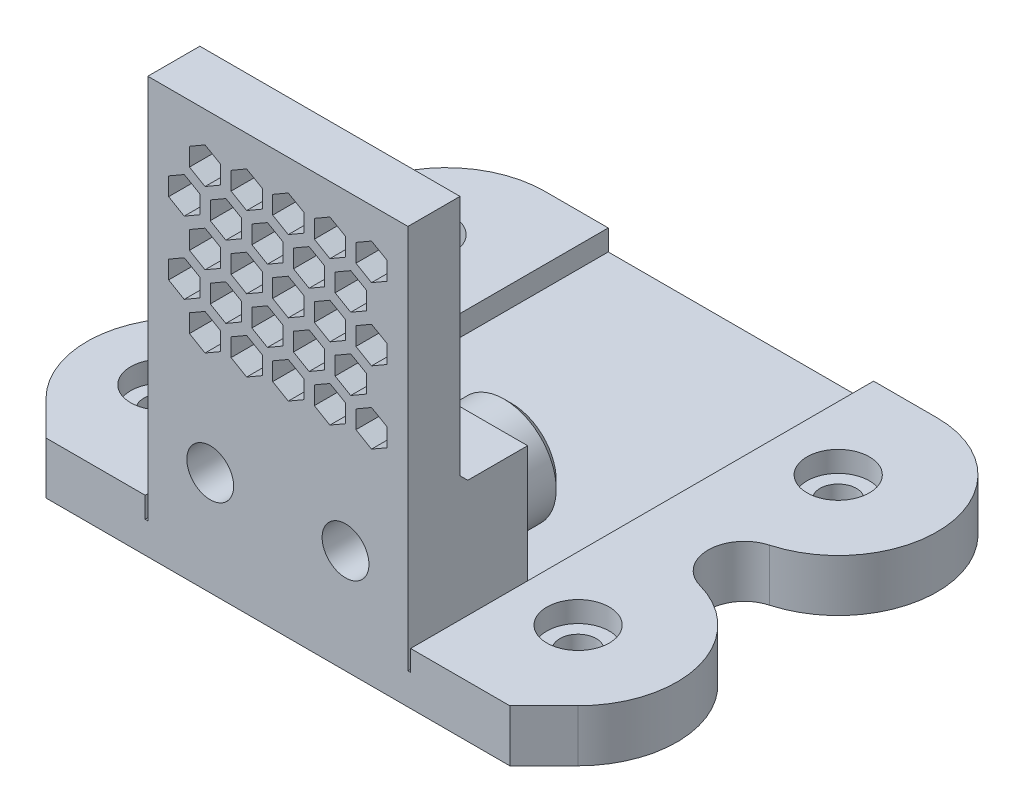
SolidWorks part; units mm, degrees
ref_plane "Front Plane" through (0, 0, 0) normal (0, 0, 1) x (1, 0, 0)
ref_plane "Top Plane" through (0, 0, 0) normal (0, 1, 0) x (1, 0, 0)
ref_plane "Right Plane" through (0, 0, 0) normal (1, 0, 0) x (0, 0, -1)
sketch "Sketch1" plane through (0, 0, 0) normal (1, 0, 0) x (0, 0, -1)
  line L0 (0, 0) -> (0, 40)
  line L1 (0, 40) -> (5, 40)
  line L2 (5, 40) -> (5, 16.75)
  line L3 (5, 16.75) -> (5.75, 16)
  line L4 (5.75, 16) -> (11.5, 16)
  line L5 (11.5, 16) -> (11.5, 3)
  line L6 (11.5, 3) -> (44.5, 3)
  line L7 (44.5, 3) -> (44.5, 0)
  line L8 (44.5, 0) -> (0, 0)
  line L9 (11.5, 3) -> (44, 3) construction
  line L10 (11.5, 16) -> (11.5, 3) construction
  line L11 (7, 16) -> (11.5, 16) construction
  dimension "D1" = 40
  dimension "D2" = 6.5
  dimension "D3" = 135
  dimension "D4" = 0.75
  dimension "D5" = 33
extrude "Boss-Extrude1" add sketch "Sketch1" against normal blind 25
sketch "Sketch2" plane through (0, 0, -11.5) normal (0, 0, -1) x (-1, 0, 0)
  circle A0 centre (6, 10) radius 2 construction
  circle A1 centre (6, 10) radius 5.25 construction
  circle A2 centre (6, 10) radius 5
  circle A3 centre (6, 10) radius 2.25
  circle A4 centre (19, 10) radius 5.4 construction
  circle A5 centre (6, 10) radius 2.75 construction
  circle A6 centre (19, 10) radius 2.25
  circle A7 centre (19, 10) radius 5
  dimension "D3" = 4
  dimension "D4" = 10
  dimension "D1" = 0.25
  dimension "D2" = 0.25
extrude "Boss-Extrude2" add sketch "Sketch2" along normal blind 4.5
chamfer "Chamfer1" distance 0.75 angle 45 2 edges at (-6, 15, -16) (-19, 15, -16)
extrude "Cut-Extrude1" cut sketch "Sketch2<2>" against normal up to next contours A3 | A6 region at (-6, 10, -11.5) region at (-19, 10, -11.5)
sketch "Sketch2<2>" plane through (0, 0, -11.5) normal (0, 0, -1) x (-1, 0, 0) same geometry as "Sketch2"
sketch "Sketch3" plane through (0, 3, 0) normal (0, 1, 0) x (1, 0, 0)
  line L0 (0, 44.5) -> (6.35, 44.5)
  line L1 (-12.5, 44.5) -> (-12.5, 11.5) construction
  line L2 (-25, 44.5) -> (0, 44.5) construction
  line L3 (-25, 11.5) -> (0, 11.5) construction
  line L4 (6.35, 44.5) -> (6.35, 0.5) construction
  line L5 (13.0675, 3.2825) -> (9.785, 0)
  line L6 (9.785, 0) -> (0, 0)
  line L7 (0, 0) -> (0, 11.5)
  line L8 (0, 11.5) -> (-25, 11.5)
  line L9 (0, 44.5) -> (-25, 44.5)
  line L10 (-25, 0) -> (-25, 11.5)
  line L11 (-34.785, 0) -> (-25, 0)
  line L12 (-38.0675, 3.2825) -> (-34.785, 0)
  line L13 (-25, 44.5) -> (-31.35, 44.5)
  arc A0 (6.35, 44.5) -> (8.8936, 25.8469) centre (6.35, 35) cw
  arc A1 (8.8936, 25.8469) -> (8.8936, 19.1531) centre (9.8237, 22.5) ccw
  arc A2 (8.8936, 19.1531) -> (13.0675, 3.2825) centre (6.35, 10) cw
  circle A3 centre (-33.65, 10) radius 1.75 construction
  circle A4 centre (6.35, 10) radius 1.75
  arc A6 (13.0675, 3.2825) -> (6.35, 0.5) centre (6.35, 10) cw construction
  circle A7 centre (6.35, 35) radius 1.75
  arc A10 (-33.8936, 19.1531) -> (-38.0675, 3.2825) centre (-31.35, 10) ccw
  arc A11 (-33.8936, 25.8469) -> (-33.8936, 19.1531) centre (-34.8237, 22.5) cw
  arc A12 (-31.35, 44.5) -> (-33.8936, 25.8469) centre (-31.35, 35) ccw
  circle A13 centre (6.35, 35) radius 1.75 construction
  circle A14 centre (-33.65, 10) radius 1.75
  circle A15 centre (-33.65, 35) radius 1.75
  circle A18 centre (6.35, 10) radius 1.75 construction
  circle A19 centre (-33.65, 35) radius 1.75 construction
  point P22 (6.35, 22.5)
  point P37 (-31.35, 22.5)
  dimension "D2" = 3.5
  dimension "D1" = 135
extrude "Boss-Extrude3" add sketch "Sketch3" against normal up to surface (3 mm away) up to face at (-12.5, 0, -22.25)
sketch "Sketch4" plane through (0, 3, 0) normal (0, 1, 0) x (1, 0, 0)
  line L0 (-34.785, 0) -> (-25, 0) construction
  line L1 (-38.0675, 3.2825) -> (-34.785, 0) construction
  line L2 (-31.35, 44.5) -> (6.35, 44.5) construction
  line L3 (9.785, 0) -> (13.0675, 3.2825) construction
  line L5 (-34.785, 0) -> (-25.25, 0)
  line L6 (-38.0675, 3.2825) -> (-34.785, 0)
  line L7 (-31.35, 44.5) -> (-25.25, 44.5)
  line L8 (9.785, 0) -> (13.0675, 3.2825)
  line L10 (-25, 0) -> (-25, 11.5) construction
  line L11 (0, 11.5) -> (0, 0) construction
  line L20 (-25, 0) -> (-25, 11.5) construction
  line L21 (0, 11.5) -> (0, 0) construction
  line L22 (0.25, 44.5) -> (0.25, 0)
  line L23 (0.25, 11.5) -> (0.25, 0) construction
  line L24 (-25.25, 0) -> (-25.25, 44.5)
  line L25 (-25.25, 0) -> (-25.25, 11.5) construction
  line L26 (0.25, 44.5) -> (6.35, 44.5)
  line L27 (-25.25, 44.5) -> (0.25, 44.5) construction
  line L28 (0.25, 0) -> (9.785, 0)
  arc A0 (-33.8936, 19.1531) -> (-38.0675, 3.2825) centre (-31.35, 10) ccw construction
  arc A1 (-33.8936, 19.1531) -> (-33.8936, 25.8469) centre (-34.8237, 22.5) ccw construction
  arc A2 (-31.35, 44.5) -> (-33.8936, 25.8469) centre (-31.35, 35) ccw construction
  arc A3 (8.8936, 25.8469) -> (6.35, 44.5) centre (6.35, 35) ccw construction
  arc A4 (8.8936, 25.8469) -> (8.8936, 19.1531) centre (9.8237, 22.5) ccw construction
  arc A5 (13.0675, 3.2825) -> (8.8936, 19.1531) centre (6.35, 10) ccw construction
  arc A6 (-33.8936, 19.1531) -> (-38.0675, 3.2825) centre (-31.35, 10) ccw
  arc A7 (-33.8936, 19.1531) -> (-33.8936, 25.8469) centre (-34.8237, 22.5) ccw
  arc A8 (-31.35, 44.5) -> (-33.8936, 25.8469) centre (-31.35, 35) ccw
  arc A9 (8.8936, 25.8469) -> (6.35, 44.5) centre (6.35, 35) ccw
  arc A10 (8.8936, 25.8469) -> (8.8936, 19.1531) centre (9.8237, 22.5) ccw
  arc A11 (13.0675, 3.2825) -> (8.8936, 19.1531) centre (6.35, 10) ccw
  circle A12 centre (6.35, 10) radius 2.75 construction
  circle A13 centre (6.35, 35) radius 3
  circle A16 centre (6.35, 10) radius 3
  circle A19 centre (-33.65, 10) radius 3
  circle A20 centre (-33.65, 35) radius 3
  circle A21 centre (-33.65, 35) radius 1.75 construction
  circle A22 centre (-33.65, 10) radius 1.75 construction
  line M26 (0, 0) -> (9.785, 0)
  line M27 (9.785, 0) -> (13.0675, 3.2825)
  arc M28 (13.0675, 3.2825) -> (8.8936, 19.1531) centre (6.35, 10) ccw
  arc M29 (8.8936, 19.1531) -> (8.8936, 25.8469) centre (9.8237, 22.5) cw
  arc M30 (8.8936, 25.8469) -> (6.35, 44.5) centre (6.35, 35) ccw
  line M31 (6.35, 44.5) -> (-31.35, 44.5)
  arc M32 (-31.35, 44.5) -> (-33.8936, 25.8469) centre (-31.35, 35) ccw
  arc M33 (-33.8936, 25.8469) -> (-33.8936, 19.1531) centre (-34.8237, 22.5) cw
  arc M34 (-33.8936, 19.1531) -> (-38.0675, 3.2825) centre (-31.35, 10) ccw
  line M35 (-38.0675, 3.2825) -> (-34.785, 0)
  line M36 (-34.785, 0) -> (-25, 0)
  dimension "D1" = 0.25
  dimension "D2" = 0.25
  dimension "D4" = 5.5
  dimension "D3" = 0.25
extrude "Boss-Extrude4" add sketch "Sketch4" along normal blind 2 contours L22 A16 A13 M31 M26 M27 M28 M29 M30 | A20 L24 A19 M31 M32 M33 M34 M35 M36 region at (-36.0928, 3, -1.9747) region at (3.3, 3, -44.0284)
sketch "Sketch5" plane through (0, 0, -5) normal (0, 0, -1) x (-1, 0, 0)
  line L0 (2, 37.0353) -> (0, 37.0353) construction
  line L1 (3.5, 19.7147) -> (5, 20.5808)
  line L2 (5, 20.5808) -> (5, 22.3128)
  line L3 (5, 22.3128) -> (3.5, 23.1788)
  line L4 (3.5, 23.1788) -> (2, 22.3128)
  line L5 (2, 22.3128) -> (2, 20.5808)
  line L6 (2, 20.5808) -> (3.5, 19.7147)
  line L7 (2, 19.7147) -> (23, 19.7147) construction
  line L8 (2, 19.7147) -> (2, 37.0353) construction
  line L9 (2, 37.0353) -> (23, 37.0353) construction
  line L11 (0, 16.75) -> (0, 40) construction
  line L12 (2, 40) -> (2, 37.0353) construction
  line L13 (25, 40) -> (0, 40) construction
  line L14 (25, 19.7147) -> (23, 19.7147) construction
  line L15 (25, 16.75) -> (25, 40) construction
  line L16 (23, 19.7147) -> (23, 16.75) construction
  line L17 (25, 16.75) -> (0, 16.75) construction
  line L60 (3.5, 21.4468) -> (-5.5, 37.0353) construction
  line L61 (-5.5, 37.0353) -> (0, 37.0353) construction
  line L302 (9, 22.3128) -> (7.5, 23.1788)
  line L303 (9, 20.5808) -> (9, 22.3128)
  line L304 (7.5, 19.7147) -> (9, 20.5808)
  line L305 (6, 20.5808) -> (7.5, 19.7147)
  line L306 (6, 22.3128) -> (6, 20.5808)
  line L307 (7.5, 23.1788) -> (6, 22.3128)
  line L308 (13, 22.3128) -> (11.5, 23.1788)
  line L309 (13, 20.5808) -> (13, 22.3128)
  line L310 (11.5, 19.7147) -> (13, 20.5808)
  line L311 (10, 20.5808) -> (11.5, 19.7147)
  line L312 (10, 22.3128) -> (10, 20.5808)
  line L313 (11.5, 23.1788) -> (10, 22.3128)
  line L314 (17, 22.3128) -> (15.5, 23.1788)
  line L315 (17, 20.5808) -> (17, 22.3128)
  line L316 (15.5, 19.7147) -> (17, 20.5808)
  line L317 (14, 20.5808) -> (15.5, 19.7147)
  line L318 (14, 22.3128) -> (14, 20.5808)
  line L319 (15.5, 23.1788) -> (14, 22.3128)
  line L320 (21, 22.3128) -> (19.5, 23.1788)
  line L321 (21, 20.5808) -> (21, 22.3128)
  line L322 (19.5, 19.7147) -> (21, 20.5808)
  line L323 (18, 20.5808) -> (19.5, 19.7147)
  line L324 (18, 22.3128) -> (18, 20.5808)
  line L325 (19.5, 23.1788) -> (18, 22.3128)
  line L326 (25, 22.3128) -> (23.5, 23.1788) [skipped]
  line L327 (25, 20.5808) -> (25, 22.3128) [skipped]
  line L328 (23.5, 19.7147) -> (25, 20.5808) [skipped]
  line L329 (22, 20.5808) -> (23.5, 19.7147) [skipped]
  line L330 (22, 22.3128) -> (22, 20.5808) [skipped]
  line L331 (23.5, 23.1788) -> (22, 22.3128) [skipped]
  line L332 (29, 22.3128) -> (27.5, 23.1788) [skipped]
  line L333 (29, 20.5808) -> (29, 22.3128) [skipped]
  line L334 (27.5, 19.7147) -> (29, 20.5808) [skipped]
  line L335 (26, 20.5808) -> (27.5, 19.7147) [skipped]
  line L336 (26, 22.3128) -> (26, 20.5808) [skipped]
  line L337 (27.5, 23.1788) -> (26, 22.3128) [skipped]
  line L338 (7, 25.7769) -> (5.5, 26.6429)
  line L339 (7, 24.0449) -> (7, 25.7769)
  line L340 (5.5, 23.1788) -> (7, 24.0449)
  line L341 (4, 24.0449) -> (5.5, 23.1788)
  line L342 (4, 25.7769) -> (4, 24.0449)
  line L343 (5.5, 26.6429) -> (4, 25.7769)
  line L344 (11, 25.7769) -> (9.5, 26.6429)
  line L345 (11, 24.0449) -> (11, 25.7769)
  line L346 (9.5, 23.1788) -> (11, 24.0449)
  line L347 (8, 24.0449) -> (9.5, 23.1788)
  line L348 (8, 25.7769) -> (8, 24.0449)
  line L349 (9.5, 26.6429) -> (8, 25.7769)
  line L350 (15, 25.7769) -> (13.5, 26.6429)
  line L351 (15, 24.0449) -> (15, 25.7769)
  line L352 (13.5, 23.1788) -> (15, 24.0449)
  line L353 (12, 24.0449) -> (13.5, 23.1788)
  line L354 (12, 25.7769) -> (12, 24.0449)
  line L355 (13.5, 26.6429) -> (12, 25.7769)
  line L356 (19, 25.7769) -> (17.5, 26.6429)
  line L357 (19, 24.0449) -> (19, 25.7769)
  line L358 (17.5, 23.1788) -> (19, 24.0449)
  line L359 (16, 24.0449) -> (17.5, 23.1788)
  line L360 (16, 25.7769) -> (16, 24.0449)
  line L361 (17.5, 26.6429) -> (16, 25.7769)
  line L362 (23, 25.7769) -> (21.5, 26.6429)
  line L363 (23, 24.0449) -> (23, 25.7769)
  line L364 (21.5, 23.1788) -> (23, 24.0449)
  line L365 (20, 24.0449) -> (21.5, 23.1788)
  line L366 (20, 25.7769) -> (20, 24.0449)
  line L367 (21.5, 26.6429) -> (20, 25.7769)
  line L368 (27, 25.7769) -> (25.5, 26.6429) [skipped]
  line L369 (27, 24.0449) -> (27, 25.7769) [skipped]
  line L370 (25.5, 23.1788) -> (27, 24.0449) [skipped]
  line L371 (24, 24.0449) -> (25.5, 23.1788) [skipped]
  line L372 (24, 25.7769) -> (24, 24.0449) [skipped]
  line L373 (25.5, 26.6429) -> (24, 25.7769) [skipped]
  line L374 (5, 29.241) -> (3.5, 30.1071)
  line L375 (5, 27.509) -> (5, 29.241)
  line L376 (3.5, 26.6429) -> (5, 27.509)
  line L377 (2, 27.509) -> (3.5, 26.6429)
  line L378 (2, 29.241) -> (2, 27.509)
  line L379 (3.5, 30.1071) -> (2, 29.241)
  line L380 (9, 29.241) -> (7.5, 30.1071)
  line L381 (9, 27.509) -> (9, 29.241)
  line L382 (7.5, 26.6429) -> (9, 27.509)
  line L383 (6, 27.509) -> (7.5, 26.6429)
  line L384 (6, 29.241) -> (6, 27.509)
  line L385 (7.5, 30.1071) -> (6, 29.241)
  line L386 (13, 29.241) -> (11.5, 30.1071)
  line L387 (13, 27.509) -> (13, 29.241)
  line L388 (11.5, 26.6429) -> (13, 27.509)
  line L389 (10, 27.509) -> (11.5, 26.6429)
  line L390 (10, 29.241) -> (10, 27.509)
  line L391 (11.5, 30.1071) -> (10, 29.241)
  line L392 (17, 29.241) -> (15.5, 30.1071)
  line L393 (17, 27.509) -> (17, 29.241)
  line L394 (15.5, 26.6429) -> (17, 27.509)
  line L395 (14, 27.509) -> (15.5, 26.6429)
  line L396 (14, 29.241) -> (14, 27.509)
  line L397 (15.5, 30.1071) -> (14, 29.241)
  line L398 (21, 29.241) -> (19.5, 30.1071)
  line L399 (21, 27.509) -> (21, 29.241)
  line L400 (19.5, 26.6429) -> (21, 27.509)
  line L401 (18, 27.509) -> (19.5, 26.6429)
  line L402 (18, 29.241) -> (18, 27.509)
  line L403 (19.5, 30.1071) -> (18, 29.241)
  line L404 (25, 29.241) -> (23.5, 30.1071) [skipped]
  line L405 (25, 27.509) -> (25, 29.241) [skipped]
  line L406 (23.5, 26.6429) -> (25, 27.509) [skipped]
  line L407 (22, 27.509) -> (23.5, 26.6429) [skipped]
  line L408 (22, 29.241) -> (22, 27.509) [skipped]
  line L409 (23.5, 30.1071) -> (22, 29.241) [skipped]
  line L410 (3, 32.7051) -> (1.5, 33.5712) [skipped]
  line L411 (3, 30.9731) -> (3, 32.7051) [skipped]
  line L412 (1.5, 30.1071) -> (3, 30.9731) [skipped]
  line L413 (0, 30.9731) -> (1.5, 30.1071) [skipped]
  line L414 (0, 32.7051) -> (0, 30.9731) [skipped]
  line L415 (1.5, 33.5712) -> (0, 32.7051) [skipped]
  line L416 (7, 32.7051) -> (5.5, 33.5712)
  line L417 (7, 30.9731) -> (7, 32.7051)
  line L418 (5.5, 30.1071) -> (7, 30.9731)
  line L419 (4, 30.9731) -> (5.5, 30.1071)
  line L420 (4, 32.7051) -> (4, 30.9731)
  line L421 (5.5, 33.5712) -> (4, 32.7051)
  line L422 (11, 32.7051) -> (9.5, 33.5712)
  line L423 (11, 30.9731) -> (11, 32.7051)
  line L424 (9.5, 30.1071) -> (11, 30.9731)
  line L425 (8, 30.9731) -> (9.5, 30.1071)
  line L426 (8, 32.7051) -> (8, 30.9731)
  line L427 (9.5, 33.5712) -> (8, 32.7051)
  line L428 (15, 32.7051) -> (13.5, 33.5712)
  line L429 (15, 30.9731) -> (15, 32.7051)
  line L430 (13.5, 30.1071) -> (15, 30.9731)
  line L431 (12, 30.9731) -> (13.5, 30.1071)
  line L432 (12, 32.7051) -> (12, 30.9731)
  line L433 (13.5, 33.5712) -> (12, 32.7051)
  line L434 (19, 32.7051) -> (17.5, 33.5712)
  line L435 (19, 30.9731) -> (19, 32.7051)
  line L436 (17.5, 30.1071) -> (19, 30.9731)
  line L437 (16, 30.9731) -> (17.5, 30.1071)
  line L438 (16, 32.7051) -> (16, 30.9731)
  line L439 (17.5, 33.5712) -> (16, 32.7051)
  line L440 (23, 32.7051) -> (21.5, 33.5712)
  line L441 (23, 30.9731) -> (23, 32.7051)
  line L442 (21.5, 30.1071) -> (23, 30.9731)
  line L443 (20, 30.9731) -> (21.5, 30.1071)
  line L444 (20, 32.7051) -> (20, 30.9731)
  line L445 (21.5, 33.5712) -> (20, 32.7051)
  line L446 (1, 36.1692) -> (-0.5, 37.0353) [skipped]
  line L447 (1, 34.4372) -> (1, 36.1692) [skipped]
  line L448 (-0.5, 33.5712) -> (1, 34.4372) [skipped]
  line L449 (-2, 34.4372) -> (-0.5, 33.5712) [skipped]
  line L450 (-2, 36.1692) -> (-2, 34.4372) [skipped]
  line L451 (-0.5, 37.0353) -> (-2, 36.1692) [skipped]
  line L452 (5, 36.1692) -> (3.5, 37.0353)
  line L453 (5, 34.4372) -> (5, 36.1692)
  line L454 (3.5, 33.5712) -> (5, 34.4372)
  line L455 (2, 34.4372) -> (3.5, 33.5712)
  line L456 (2, 36.1692) -> (2, 34.4372)
  line L457 (3.5, 37.0353) -> (2, 36.1692)
  line L458 (9, 36.1692) -> (7.5, 37.0353)
  line L459 (9, 34.4372) -> (9, 36.1692)
  line L460 (7.5, 33.5712) -> (9, 34.4372)
  line L461 (6, 34.4372) -> (7.5, 33.5712)
  line L462 (6, 36.1692) -> (6, 34.4372)
  line L463 (7.5, 37.0353) -> (6, 36.1692)
  line L464 (13, 36.1692) -> (11.5, 37.0353)
  line L465 (13, 34.4372) -> (13, 36.1692)
  line L466 (11.5, 33.5712) -> (13, 34.4372)
  line L467 (10, 34.4372) -> (11.5, 33.5712)
  line L468 (10, 36.1692) -> (10, 34.4372)
  line L469 (11.5, 37.0353) -> (10, 36.1692)
  line L470 (17, 36.1692) -> (15.5, 37.0353)
  line L471 (17, 34.4372) -> (17, 36.1692)
  line L472 (15.5, 33.5712) -> (17, 34.4372)
  line L473 (14, 34.4372) -> (15.5, 33.5712)
  line L474 (14, 36.1692) -> (14, 34.4372)
  line L475 (15.5, 37.0353) -> (14, 36.1692)
  line L476 (21, 36.1692) -> (19.5, 37.0353)
  line L477 (21, 34.4372) -> (21, 36.1692)
  line L478 (19.5, 33.5712) -> (21, 34.4372)
  line L479 (18, 34.4372) -> (19.5, 33.5712)
  line L480 (18, 36.1692) -> (18, 34.4372)
  line L481 (19.5, 37.0353) -> (18, 36.1692)
  line L482 (3, 25.7769) -> (1.5, 26.6429) [skipped]
  line L483 (3, 24.0449) -> (3, 25.7769) [skipped]
  line L484 (1.5, 23.1788) -> (3, 24.0449) [skipped]
  line L485 (0, 24.0449) -> (1.5, 23.1788) [skipped]
  line L486 (0, 25.7769) -> (0, 24.0449) [skipped]
  line L487 (1.5, 26.6429) -> (0, 25.7769) [skipped]
  line L488 (1, 29.241) -> (-0.5, 30.1071) [skipped]
  line L489 (1, 27.509) -> (1, 29.241) [skipped]
  line L490 (-0.5, 26.6429) -> (1, 27.509) [skipped]
  line L491 (-2, 27.509) -> (-0.5, 26.6429) [skipped]
  line L492 (-2, 29.241) -> (-2, 27.509) [skipped]
  line L493 (-0.5, 30.1071) -> (-2, 29.241) [skipped]
  line L494 (-1, 32.7051) -> (-2.5, 33.5712) [skipped]
  line L495 (-1, 30.9731) -> (-1, 32.7051) [skipped]
  line L496 (-2.5, 30.1071) -> (-1, 30.9731) [skipped]
  line L497 (-4, 30.9731) -> (-2.5, 30.1071) [skipped]
  line L498 (-4, 32.7051) -> (-4, 30.9731) [skipped]
  line L499 (-2.5, 33.5712) -> (-4, 32.7051) [skipped]
  line L500 (-3, 36.1692) -> (-4.5, 37.0353) [skipped]
  line L501 (-3, 34.4372) -> (-3, 36.1692) [skipped]
  line L502 (-4.5, 33.5712) -> (-3, 34.4372) [skipped]
  line L503 (-6, 34.4372) -> (-4.5, 33.5712) [skipped]
  line L504 (-6, 36.1692) -> (-6, 34.4372) [skipped]
  line L505 (-4.5, 37.0353) -> (-6, 36.1692) [skipped]
  line L506 (23, 37.0353) -> (23, 19.7147) construction
  circle A0 centre (3.5, 21.4468) radius 1.5 construction
  point P19 (4.75, 23.6119)
  dimension "D2" = 3
  dimension "D4" = 7
  dimension "D6" = 1
  dimension "D5" = 5
  dimension "D7" = 1
  dimension "D8" = 1
extrude "Cut-Extrude2" cut sketch "Sketch5" against normal up to next (5 mm away)
equation "\"Tolerance\" = 0.25mm"
equation "\"Pocket_Head_M5\"= 8mm"
equation "\"Pocket_Head_M4\" = 7mm"
equation "\"Pocket_Nut_M4\" = 7mm"
equation "\"Pocket_Nut_M5\"= 8mm"
equation "\"Pocket_Nut_M3\"= 5.5mm"
equation "\"Pocket_Head_M3\"= 5.5mm"
equation "\"D1@Sketch2\"=\"Tolerance\""
equation "\"D2@Sketch2\"=\"Tolerance\""
equation "\"D1@Sketch4\"=\"Tolerance\""
equation "\"D2@Sketch4\"=\"Tolerance\""
equation "\"D3@Sketch4\"=\"Tolerance\""
equation "\"D4@Sketch4\"=\"Pocket_Head_M3\""
